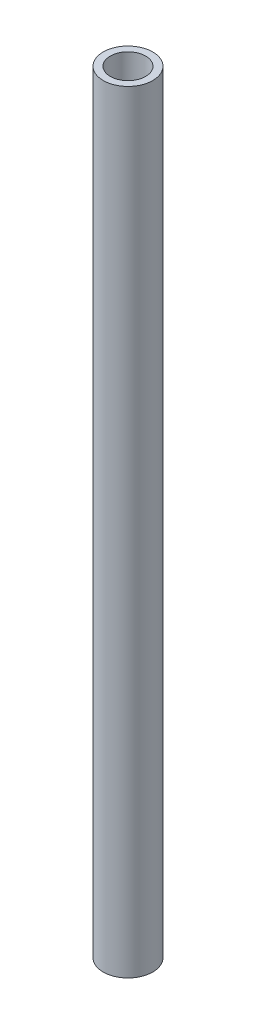
SolidWorks part; units mm, degrees
ref_plane "Front Plane" through (0, 0, 0) normal (0, 0, 1) x (1, 0, 0)
ref_plane "Top Plane" through (0, 0, 0) normal (0, 1, 0) x (1, 0, 0)
ref_plane "Right Plane" through (0, 0, 0) normal (1, 0, 0) x (0, 0, -1)
sketch "Sketch1" plane through (0, 0, 0) normal (0, 1, 0) x (1, 0, 0)
  circle A0 centre (0, 0) radius 1.925
  dimension "D1" = 3.85
extrude "Boss-Extrude1" add sketch "Sketch1" along normal blind 60
sketch "Sketch2" plane through (0, 60, 0) normal (0, 1, 0) x (1, 0, 0)
  circle A0 centre (0, 0) radius 1.375
  dimension "D1" = 2.75
extrude "Cut-Extrude1" cut sketch "Sketch2" against normal blind 11
extrude "Cut-Extrude2" cut sketch "Sketch2<2>" along normal blind 11 from surface starting at face at (0, 0, 1.925)
sketch "Sketch2<2>" plane through (0, 60, 0) normal (0, 1, 0) x (1, 0, 0) same geometry as "Sketch2"
